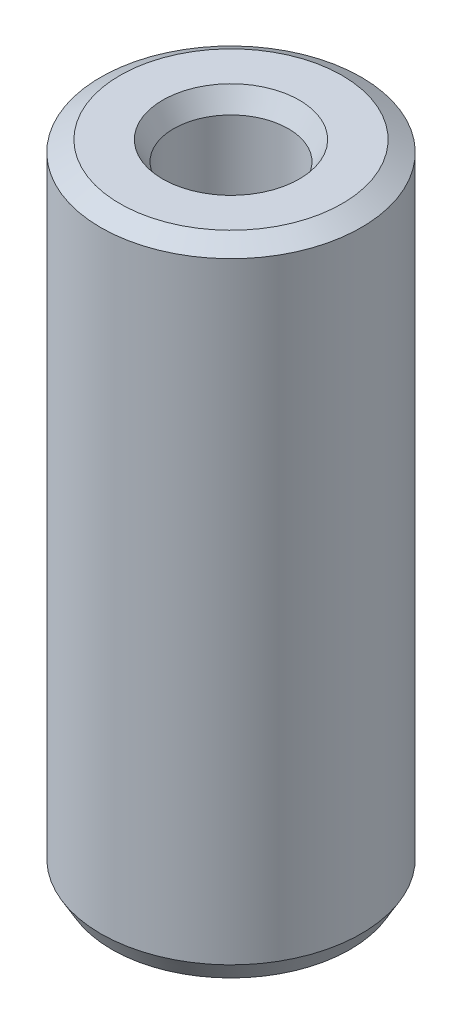
SolidWorks part; units mm, degrees
ref_plane "Front Plane" through (0, 0, 0) normal (0, 0, 1) x (1, 0, 0)
ref_plane "Top Plane" through (0, 0, 0) normal (0, 1, 0) x (1, 0, 0)
ref_plane "Right Plane" through (0, 0, 0) normal (1, 0, 0) x (0, 0, -1)
sketch "Sketch1" plane through (0, 0, 0) normal (0, 1, 0) x (1, 0, 0)
  circle A0 centre (0, 0) radius 40
  dimension "SLEEVE_OD" = 80
extrude "Boss-Extrude1" add sketch "Sketch1" along normal blind 197.0491
sketch "Sketch2" plane through (0, 0, 0) normal (0, 1, 0) x (1, 0, 0)
  circle A0 centre (0, 0) radius 17.5938
  dimension "BORE_D" = 35.1875
extrude "Cut-Extrude1" cut sketch "Sketch2" along normal through all
chamfer "Chamfer1" distance 3.399 angle 60 4 edges at (0, 197.0491, 17.5938) (0, 0, 17.5938) (0, 0, 40) (0, 197.0491, 40) first distance on face at (0, 197.0491, 17.5938) first distance on face at (0, 0, 17.5938) first distance on face at (0, 197.0491, 40)
